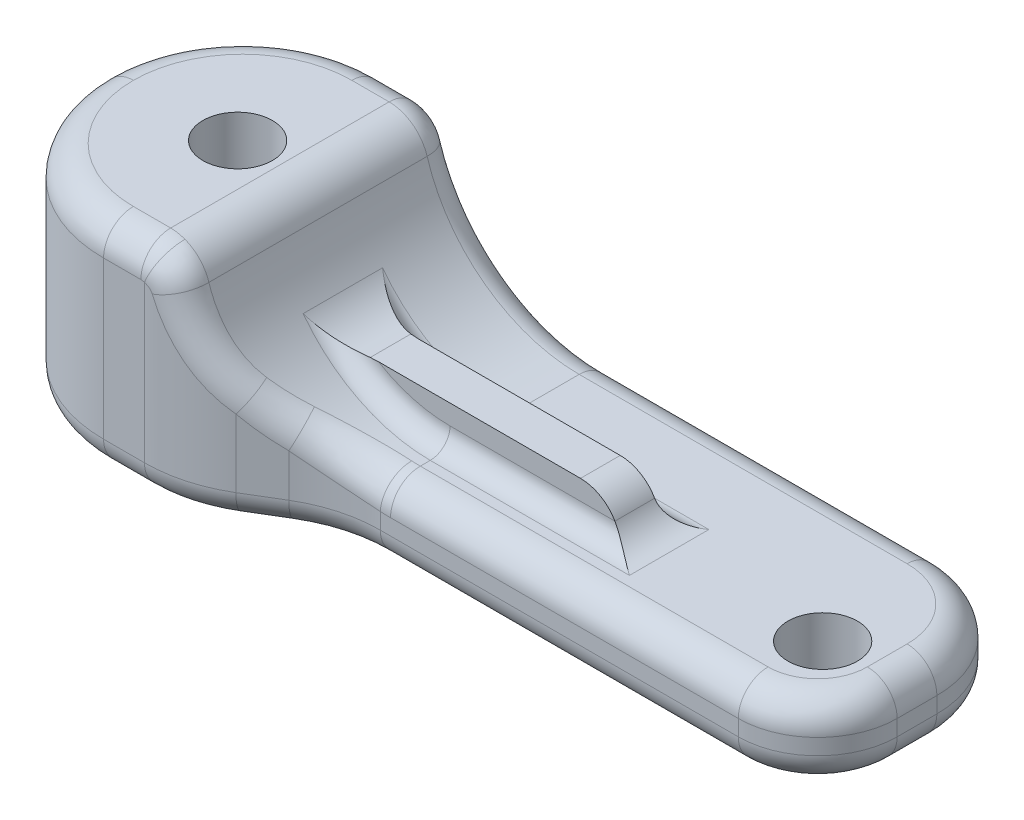
SolidWorks part; units mm, degrees
material "ABS"
ref_plane "Front Plane" through (0, 0, 0) normal (0, 0, 1) x (1, 0, 0)
ref_plane "Top Plane" through (0, 0, 0) normal (0, 1, 0) x (1, 0, 0)
ref_plane "Right Plane" through (0, 0, 0) normal (1, 0, 0) x (0, 0, -1)
sketch "Sketch1" plane through (0, 0, 0) normal (0, 1, 0) x (1, 0, 0)
  line L1 (-18.4809, 4) -> (18.4809, 4)
  line L2 (-18.4809, 4) -> (-18.4809, -4)
  line L3 (-18.4809, -4) -> (18.4809, -4)
  line L4 (18.4809, 4) -> (18.4809, -4)
  line L5 (-18.4809, 4) -> (18.4809, -4) construction
  line L6 (-18.4809, -4) -> (18.4809, 4) construction
  point P0 (0, 0)
  dimension "D1" = 8
  dimension "D2" = 36.9619
extrude "Boss-Extrude1" add sketch "Sketch1" along normal blind 3.8
sketch "Sketch2" plane through (0, 3.8, 0) normal (0, 1, 0) x (1, 0, 0)
  line L0 (0, 0) -> (14.7309, 0) construction
  line L1 (0, 0) -> (-14.7309, 0) construction
  line L3 (-18.4809, 4) -> (-18.4809, -4) construction
  line L4 (18.4809, -4) -> (18.4809, 4) construction
  circle A0 centre (-14.7309, 0) radius 1.75
  circle A1 centre (14.7309, 0) radius 1.75
  dimension "D3" = 3.5
  dimension "D4" = 3.5
  dimension "D1" = 3.75
  dimension "D2" = 3.75
extrude "Cut-Extrude1" cut sketch "Sketch2" against normal through all
sketch "Sketch3" plane through (0, 0, 0) normal (0, -1, 0) x (1, 0, 0)
  line L1 (-10.9809, 4) -> (-18.4809, 4)
  line L2 (-10.9809, 4) -> (-10.9809, -4)
  line L3 (-10.9809, -4) -> (-18.4809, -4)
  line L4 (-18.4809, 4) -> (-18.4809, -4)
  line L5 (-10.9809, 4) -> (-18.4809, -4) construction
  line L6 (-10.9809, -4) -> (-18.4809, 4) construction
  circle A1 centre (-14.7309, 0) radius 1.75 construction
  circle A2 centre (-14.7309, 0) radius 1.75
extrude "Boss-Extrude2" add sketch "Sketch3" along normal blind 7.1
sketch "Sketch4" plane through (0, 3.8, 0) normal (0, 1, 0) x (1, 0, 0)
  line L1 (-5, 1) -> (5, 1)
  line L2 (-5, 1) -> (-5, -1) construction
  line L3 (-5, -1) -> (5, -1)
  line L4 (5, 1) -> (5, -1)
  line L5 (-5, 1) -> (5, -1) construction
  line L6 (-5, -1) -> (5, 1) construction
  line L7 (-5, 1) -> (-9, 1)
  line L8 (-5, 1) -> (-5, -1) construction
  line L9 (-5, -1) -> (-9, -1)
  line L10 (-9, 1) -> (-9, -1)
  point P0 (0, 0)
  dimension "D1" = 10
  dimension "D2" = 2
  dimension "5" = 4
extrude "Boss-Extrude3" add sketch "Sketch4" along normal blind 2
sketch "Sketch8" plane through (0, 0, -4) normal (0, 0, -1) x (-1, 0, 0)
  line L6 (-18.4809, 0) -> (10.9809, 0)
  line L7 (10.9809, 0) -> (10.9809, -7.1)
  line L8 (10.9809, -7.1) -> (18.4809, -7.1)
  line L9 (18.4809, -7.1) -> (18.4809, 3.8)
  line L10 (18.4809, 3.8) -> (-18.4809, 3.8)
  line L11 (-18.4809, 3.8) -> (-18.4809, 0)
  line L12 (-18.4809, 0) -> (10.9809, 0)
  line L13 (10.9809, 0) -> (10.9809, -7.1)
  line L14 (10.9809, -7.1) -> (18.4809, -7.1)
  line L15 (18.4809, -7.1) -> (18.4809, 3.8)
  line L16 (18.4809, 3.8) -> (-18.4809, 3.8)
  line L17 (-18.4809, 3.8) -> (-18.4809, 0)
  dimension "D1" = 0
extrude "Boss-Extrude5" add sketch "Sketch8" along normal blind 3 contours L12 L13 L14 L15 L16 L17
sketch "Sketch9" plane through (-18.4809, 0, 0) normal (-1, 0, 0) x (0, 0, 1)
  line L4 (4, 3.8) -> (-7, 3.8)
  line L5 (-7, 3.8) -> (-7, -7.1)
  line L6 (-7, -7.1) -> (4, -7.1)
  line L7 (4, -7.1) -> (4, 3.8)
  line L8 (4, 3.8) -> (-7, 3.8)
  line L9 (-7, 3.8) -> (-7, -7.1)
  line L10 (-7, -7.1) -> (4, -7.1)
  line L11 (4, -7.1) -> (4, 3.8)
  dimension "D1" = 0
extrude "Boss-Extrude6" add sketch "Sketch9" along normal blind 3
sketch "Sketch10" plane through (0, 0, 4) normal (0, 0, 1) x (1, 0, 0)
  line L0 (-5.4809, 3.8) -> (-5.4809, 0)
  line L6 (18.4809, 3.8) -> (-21.4809, 3.8)
  line L7 (-21.4809, 3.8) -> (-21.4809, -7.1)
  line L8 (-21.4809, -7.1) -> (-10.9809, -7.1)
  line L9 (-10.9809, -7.1) -> (-10.9809, 0)
  line L10 (-10.9809, 0) -> (18.4809, 0)
  line L11 (18.4809, 0) -> (18.4809, 3.8)
  line L12 (-5.4809, 3.8) -> (-21.4809, 3.8)
  line L13 (-21.4809, 3.8) -> (-21.4809, -7.1)
  line L14 (-21.4809, -7.1) -> (-10.9809, -7.1)
  line L15 (-10.9809, -7.1) -> (-10.9809, 0)
  line L16 (-10.9809, 0) -> (-5.4809, 0)
  dimension "D2" = 5.5
  dimension "D1" = 0
extrude "Boss-Extrude7" add sketch "Sketch10" along normal blind 3
chamfer "Chamfer1" distance 5 angle 31 1 edges at (-5.4809, 1.9, 7) first distance on face at (-12.6476, -1.1, 7)
fillet "Fillet8" radius 4 1 edges at (18.4809, 1.9, 4)
fillet "Fillet9" radius 7 2 edges at (-21.4809, -1.65, 7) (-21.4809, -1.65, -7)
fillet "Fillet10" radius 5 1 edges at (18.4809, 1.9, -7)
fillet "Fillet11" radius 7 2 edges at (-5.4881, 1.9, 4) (-10.4809, 1.9, 7)
fillet "Fillet12" radius 8 1 edges at (-10.9809, 0, -0.075)
fillet "Fillet13" radius 2 1 edges at (-10.9809, -7.1, -0.075)
fillet "Fillet14" radius 1.5 28 edges at (17.0165, 3.8, -5.5355) (17.0165, 0, -5.5355) (18.4809, 0, -1) (18.4809, 3.8, -1) (17.3094, 3.8, 2.8284) (17.3094, 0, 2.8284) (5.7246, 0, 4) (-3.2894, -0.0042, 4) (-5.4282, -0.3674, 4.2576) (-8.0291, -1.7529, 5.5268) (-9.1546, -2.8512, 6.1906) (-11.2396, -6.5642, 6.8994) (-12.512, -7.098, 7) (-13.5415, -7.1, 7) (-19.4307, 3.8, 4.9497) (-19.4307, -7.1, 4.9497) (-19.4307, 3.8, -4.9497) (-19.4307, -7.1, -4.9497) (-13.5415, -7.1, -7) (-11.4103, -6.7062, -7) (-7.7983, -1.575, -7) (-5.4175, 3.8, 4.2546) (-7.9845, 3.8, 5.5) (-10.5515, 3.8, 6.7454) (-13.4516, 3.8, 7) (-0.5, 3.8, -7) (5.2246, 0, -7) (5.4671, 3.8, 4)
sketch "Sketch11" plane through (0, 0, 0) normal (0, -1, 0) x (1, 0, 0)
  line L1 (-5, 1) -> (5, 1)
  line L2 (-5, 1) -> (-5, -1) construction
  line L3 (-5, -1) -> (5, -1)
  line L4 (5, 1) -> (5, -1)
  line L5 (-5, 1) -> (5, -1) construction
  line L6 (-5, -1) -> (5, 1) construction
  line L7 (-5, 1) -> (-9, 1)
  line L8 (-5, 1) -> (-5, -1) construction
  line L9 (-5, -1) -> (-9, -1)
  line L10 (-9, 1) -> (-9, -1)
  point P0 (0, 0)
  dimension "D1" = 2
  dimension "D2" = 10
  dimension "D3" = 4
extrude "Boss-Extrude8" add sketch "Sketch11" along normal blind 2
fillet "Fillet5" radius 2 3 edges at (5, 3.8, 0) (-9, 3.8, 0) (5, 0, 0)
fillet "Fillet6" radius 2 3 edges at (5, 5.8, 0) (-9, 5.8, 0) (5, -2, 0)
fillet "Fillet7" radius 1 6 edges at (-2, 3.8, 1) (-2, 3.8, -1) (-5.8601, -0.5167, -1) (-5.8601, -0.5167, 1) (1.9841, 0, -1) (1.9841, 0, 1)
fillet "Fillet15" radius 3 1 edges at (-8.3232, -2, 0)
mirror "Mirror1" about plane through (0, 0, 0) normal (0, 1, 0) of bodies 110
delete or keep bodies "Body-Delete/Keep 1" type delete bodies bodies 110
